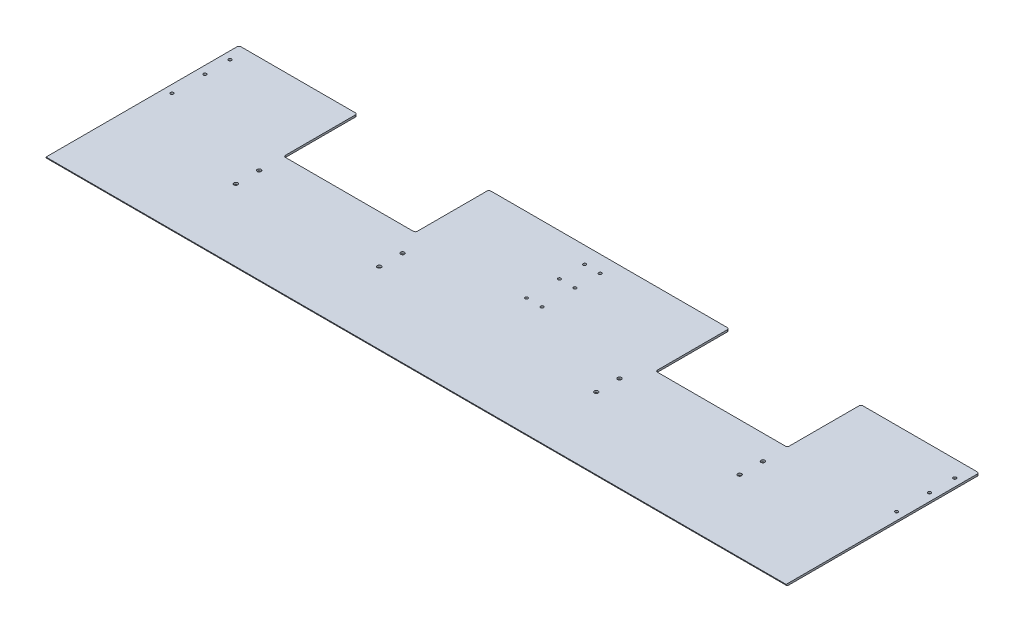
SolidWorks part; units mm, degrees
material "PE High Density"
ref_plane "Front Plane" through (0, 0, 0) normal (0, 0, 1) x (1, 0, 0)
ref_plane "Top Plane" through (0, 0, 0) normal (0, 1, 0) x (1, 0, 0)
ref_plane "Right Plane" through (0, 0, 0) normal (1, 0, 0) x (0, 0, -1)
sketch "Sketch1" plane through (0, 0, 0) normal (0, 1, 0) x (1, 0, 0)
  line L1 (0, 0) -> (1212.85, 0)
  line L2 (0, 0) -> (0, 316.23)
  line L3 (0, 316.23) -> (1212.85, 316.23)
  line L4 (1212.85, 0) -> (1212.85, 316.23)
  dimension "D1" = 1212.85
  dimension "D2" = 316.23
extrude "Boss-Extrude1" add sketch "Sketch1" along normal blind 3.175
fillet "Fillet1" radius 3.175 1 edges at (606.425, 0, 0)
hole_wizard "#10 Clearance Hole1" [suppressed] positions "Sketch2" profile "Sketch3" hole size "#10" standard "ANSI Inch"
sketch "Sketch2" plane through (0, 3.175, 0) normal (0, 1, 0) x (1, 0, 0)
  line L2 (584.2, 316.23) -> (584.2, 0) construction
  line L3 (1168.4, 316.23) -> (0, 316.23) construction
  line L6 (0, 316.23) -> (0, 0) construction
  line L7 (0, 0) -> (1168.4, 0) construction
  line L8 (0, 316.23) -> (0, 0) construction
  line L9 (1168.4, 0) -> (1168.4, 316.23) construction
  point P0 (152.4, 287.1887)
  point P7 (622.3, 287.1887)
  point P8 (1092.2, 287.1887)
  point P9 (622.3, 217.3387)
  point P10 (1092.2, 217.3387)
  point P11 (622.3, 147.4887)
  point P12 (1092.2, 147.4887)
  point P13 (152.4, 217.3387)
  point P14 (152.4, 147.4887)
  dimension "D1" = 69.85
  dimension "D5" = 147.4887
  dimension "D6" = 152.4
  dimension "D7" = 69.85
  dimension "D8" = 29.0413
  dimension "D2" = 622.3
  dimension "D3" = 76.2
sketch "Sketch3" plane through (152.4, 3.175, -287.1887) normal (1, 0, 0) x (0, 0, 1)
  line L0 (0, 0) -> (0, 3.175)
  line L1 (0, 3.175) -> (2.5527, 3.175)
  line L2 (2.5527, 3.175) -> (2.5527, 0)
  line L5 (2.5527, 0) -> (0, 0)
  line L11 (0, -6.35) -> (0, 107.95) construction
  dimension "Thru Hole Dia." = 5.1054
  dimension "Thru Hole Depth" = 3.175
sketch "Sketch4" plane through (0, 3.175, 0) normal (0, 1, 0) x (1, 0, 0)
  line L0 (1212.85, 316.23) -> (0, 316.23) construction
  line L1 (193.675, 316.23) -> (409.575, 316.23)
  line L2 (193.675, 316.23) -> (193.675, 195.58)
  line L3 (193.675, 195.58) -> (409.575, 195.58)
  line L4 (409.575, 316.23) -> (409.575, 195.58)
  line L5 (606.425, 316.23) -> (606.425, 0) construction
  line L6 (0, 0) -> (1212.85, 0) construction
  line L7 (803.275, 316.23) -> (803.275, 195.58)
  line L8 (1019.175, 195.58) -> (803.275, 195.58)
  line L9 (1019.175, 316.23) -> (1019.175, 195.58)
  line L10 (1019.175, 316.23) -> (803.275, 316.23)
  line L11 (301.625, 316.23) -> (301.625, 195.58) construction
  dimension "D1" = 215.9
  dimension "D2" = 120.65
  dimension "D3" = 304.8
extrude "Cut-Extrude1" cut sketch "Sketch4" against normal through all
fillet "Fillet2" radius 3.175 10 edges at (409.575, 1.5875, -195.58) (409.575, 1.5875, -316.23) (803.275, 1.5875, -316.23) (803.275, 1.5875, -195.58) (1019.175, 1.5875, -195.58) (1019.175, 1.5875, -316.23) (1212.85, 1.5875, -316.23) (193.675, 1.5875, -316.23) (193.675, 1.5875, -195.58) (0, 1.5875, -316.23)
hole_wizard "#10 (0.1935) Diameter Hole1" positions "Sketch5" profile "Sketch6" hole size "#10" standard "ANSI Inch" end condition through all
sketch "Sketch5" plane through (0, 3.175, 0) normal (0, 1, 0) x (1, 0, 0)
  line L0 (606.425, 0) -> (606.425, 316.23) construction
  line L1 (0, 0) -> (1212.85, 0) construction
  line L2 (800.1, 316.23) -> (412.75, 316.23) construction
  point P0 (12.7, 193.675)
  point P2 (12.7, 247.65)
  point P4 (12.7, 288.925)
  point P6 (593.725, 193.675)
  point P8 (593.725, 247.65)
  point P10 (593.725, 288.925)
  point P20 (619.125, 288.925)
  point P21 (619.125, 247.65)
  point P22 (619.125, 193.675)
  point P23 (1200.15, 288.925)
  point P24 (1200.15, 247.65)
  point P25 (1200.15, 193.675)
  dimension "D1" = 193.675
  dimension "D2" = 53.975
  dimension "D3" = 41.275
  dimension "D4" = 12.7
  dimension "D5" = 581.025
sketch "Sketch6" plane through (12.7, 3.175, -193.675) normal (1, 0, 0) x (0, 0, 1)
  line L0 (0, 0) -> (0, 3.175)
  line L1 (0, 3.175) -> (2.4574, 3.175)
  line L2 (2.4574, 3.175) -> (2.4574, 0)
  line L5 (2.4574, 0) -> (0, 0)
  line L11 (0, -6.35) -> (0, 107.95) construction
  dimension "Thru Hole Dia." = 4.9149
  dimension "Thru Hole Depth" = 3.175
hole_wizard "1/4 (0.25) Diameter Hole1" positions "Sketch7" profile "Sketch8" hole size "1/4" standard "ANSI Inch" end condition through all
sketch "Sketch7" plane through (0, 3.175, 0) normal (0, 1, 0) x (1, 0, 0)
  line L0 (606.425, 0) -> (606.425, 316.23) construction
  line L1 (0, 0) -> (1212.85, 0) construction
  line L2 (800.1, 316.23) -> (412.75, 316.23) construction
  line L4 (149.225, 150.3997) -> (1063.625, 150.3997) construction
  line L5 (149.225, 150.3997) -> (149.225, 122.6502) construction
  line L6 (149.225, 122.6502) -> (1063.625, 122.6502) construction
  line L7 (1063.625, 150.3997) -> (1063.625, 122.6502) construction
  line L8 (149.225, 136.525) -> (1063.625, 136.525) construction
  point P0 (193.675, 155.575)
  point P2 (193.675, 117.475)
  point P4 (428.625, 155.575)
  point P6 (428.625, 117.475)
  point P20 (784.225, 117.475)
  point P21 (784.225, 155.575)
  point P22 (1019.175, 117.475)
  point P23 (1019.175, 155.575)
  point P164 (606.425, 122.6502)
  point P168 (0, 0)
  point P169 (0, 0)
  point P170 (192.7262, 120.65)
  dimension "D1" = 355.6
  dimension "D2" = 38.1
  dimension "D3" = 117.475
  dimension "D4" = 914.4
  dimension "D5" = 27.7495
  dimension "D6" = 412.75
sketch "Sketch8" plane through (193.675, 3.175, -155.575) normal (1, 0, 0) x (0, 0, 1)
  line L0 (0, 0) -> (0, 3.175)
  line L1 (0, 3.175) -> (3.175, 3.175)
  line L2 (3.175, 3.175) -> (3.175, 0)
  line L5 (3.175, 0) -> (0, 0)
  line L11 (0, -6.35) -> (0, 107.95) construction
  dimension "Thru Hole Dia." = 6.35
  dimension "Thru Hole Depth" = 3.175
